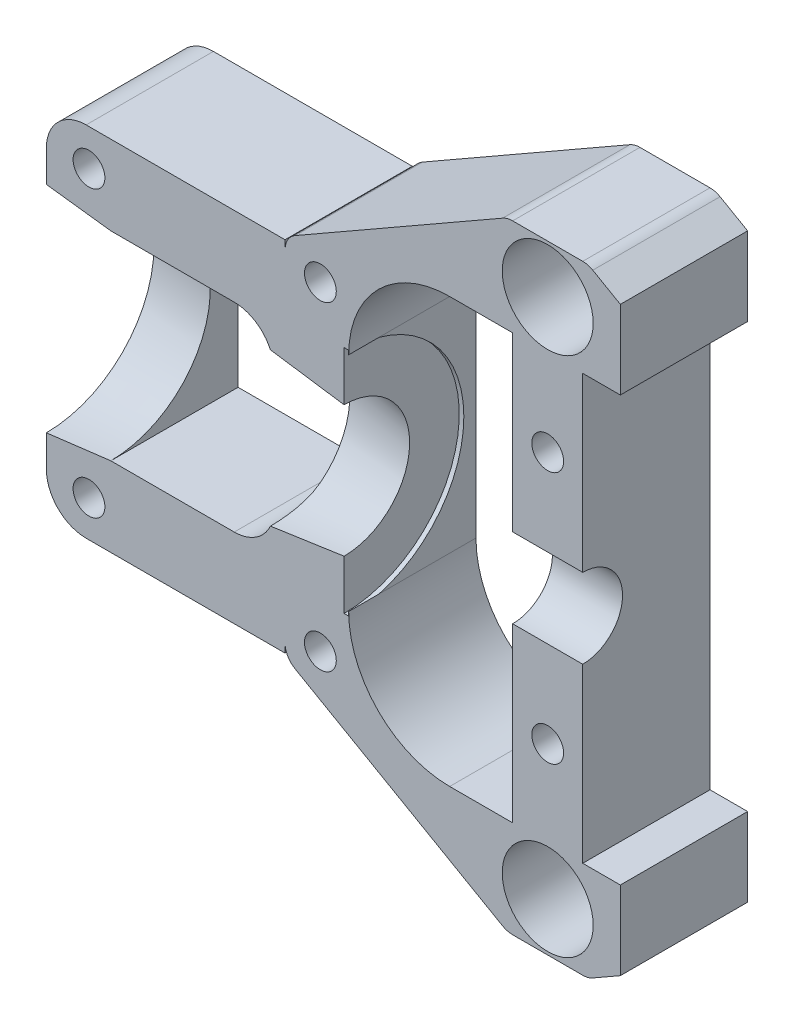
SolidWorks part; units mm, degrees
ref_plane "Front Plane" through (0, 0, 0) normal (0, 0, 1) x (1, 0, 0)
ref_plane "Top Plane" through (0, 0, 0) normal (0, 1, 0) x (1, 0, 0)
ref_plane "Right Plane" through (0, 0, 0) normal (1, 0, 0) x (0, 0, -1)
sketch "Sketch1" plane through (0, 0, 0) normal (0, 0, 1) x (1, 0, 0)
  line L0 (31.75, 34.925) -> (-31.75, 34.925) construction
  line L1 (-44.45, 22.225) -> (-44.45, -22.225) construction
  line L2 (-31.75, -34.925) -> (31.75, -34.925) construction
  line L3 (44.45, -22.225) -> (44.45, 22.225) construction
  line L4 (5.6665, -38.5261) -> (31.7424, -23.5917) construction
  line L5 (-33.02, -21.3876) -> (-33.02, 21.3876) construction
  line L6 (-31.7424, -23.5917) -> (-5.6665, -38.5261) construction
  line L7 (-4.4041, -38.862) -> (4.4041, -38.862) construction
  line L8 (33.02, -21.3876) -> (33.02, 21.3876) construction
  line L9 (5.6665, 38.5261) -> (31.7424, 23.5917) construction
  line L10 (-4.4041, 38.862) -> (4.4041, 38.862) construction
  line L11 (-5.6665, 38.5261) -> (-31.7424, 23.5917) construction
  line L12 (-33.02, -21.3876) -> (-33.02, 21.3876) construction
  line L13 (-33.02, -21.3876) -> (-33.02, 21.3876)
  line L14 (-5.6665, 38.5261) -> (-31.7424, 23.5917)
  line L15 (-4.4041, 38.862) -> (4.4041, 38.862)
  line L16 (5.6665, 38.5261) -> (31.7424, 23.5917)
  line L17 (33.02, -21.3876) -> (33.02, 21.3876)
  line L18 (-4.4041, -38.862) -> (4.4041, -38.862)
  line L19 (-31.7424, -23.5917) -> (-5.6665, -38.5261)
  line L20 (5.6665, -38.5261) -> (31.7424, -23.5917)
  line L21 (44.45, -22.225) -> (44.45, 22.225)
  line L22 (-31.75, -34.925) -> (31.75, -34.925)
  line L23 (-44.45, 22.225) -> (-44.45, -22.225)
  line L24 (31.75, 34.925) -> (-31.75, 34.925)
  line L25 (-12.319, 26.67) -> (12.319, 26.67) construction
  line L26 (25.019, 13.97) -> (25.019, -13.97) construction
  line L27 (-25.019, 13.97) -> (-25.019, -13.97) construction
  line L28 (-12.319, -26.67) -> (12.319, -26.67) construction
  line L29 (-12.319, 26.67) -> (12.319, 26.67)
  line L30 (25.019, 13.97) -> (25.019, -13.97)
  line L31 (-25.019, 13.97) -> (-25.019, -13.97)
  line L32 (-12.319, -26.67) -> (12.319, -26.67)
  line L33 (33.02, -15.875) -> (24.8753, -15.875)
  line L34 (33.02, 15.875) -> (24.8753, 15.875)
  line L35 (24.8753, 15.875) -> (24.8753, -15.875)
  line L36 (33.02, -15.875) -> (33.02, 15.875)
  line L37 (-33.02, -21.3876) -> (-33.02, 21.3876)
  line L38 (-33.02, -15.875) -> (-24.8753, -15.875)
  line L39 (-33.02, 15.875) -> (-24.8753, 15.875)
  line L40 (-33.02, 15.875) -> (-33.02, -15.875)
  line L41 (-24.8753, -15.875) -> (-24.8753, 15.875)
  line L42 (-4.4041, -38.862) -> (-4.4041, 38.862)
  line L43 (4.4041, -38.862) -> (4.4041, 38.862)
  line L44 (-12.319, 26.67) -> (12.319, 26.67) construction
  line L45 (-12.319, 26.67) -> (12.319, 26.67)
  line L46 (0, 27.051) -> (4.4041, 27.051)
  line L47 (0, 27.051) -> (-4.4041, 27.051)
  line L48 (0, -27.051) -> (-4.4041, -27.051)
  line L49 (0, -27.051) -> (4.4041, -27.051)
  line L50 (-1000, 0) -> (49000, 0) construction
  line L51 (0, -1000) -> (0, 49000) construction
  line L52 (9.1318, -26.67) -> (9.1318, -36.5414)
  line L53 (9.1318, 26.67) -> (9.1318, 36.5414)
  line L54 (-13.97, -1015.875) -> (-13.97, 48984.125) construction
  line L55 (-57.6639, -17.9107) -> (-57.6639, 17.9107) construction
  line L56 (-33.02, -22.5) -> (-63.02, -22.5)
  line L57 (-33.02, -22.5) -> (-33.02, 22.5)
  line L58 (-33.02, 22.5) -> (-63.02, 22.5)
  line L59 (-63.02, -22.5) -> (-63.02, 22.5)
  arc A0 (-5.6665, -38.5261) -> (-4.4041, -38.862) centre (-4.4041, -36.322) ccw construction
  arc A1 (-31.75, 34.925) -> (-44.45, 22.225) centre (-31.75, 22.225) ccw construction
  arc A2 (-44.45, -22.225) -> (-31.75, -34.925) centre (-31.75, -22.225) ccw construction
  arc A3 (31.75, -34.925) -> (44.45, -22.225) centre (31.75, -22.225) ccw construction
  arc A4 (44.45, 22.225) -> (31.75, 34.925) centre (31.75, 22.225) ccw construction
  arc A5 (31.7424, -23.5917) -> (33.02, -21.3876) centre (30.48, -21.3876) ccw construction
  arc A6 (33.02, 21.3876) -> (31.7424, 23.5917) centre (30.48, 21.3876) ccw construction
  arc A7 (5.6665, 38.5261) -> (4.4041, 38.862) centre (4.4041, 36.322) ccw construction
  arc A8 (-4.4041, 38.862) -> (-5.6665, 38.5261) centre (-4.4041, 36.322) ccw construction
  arc A9 (-31.7424, 23.5917) -> (-33.02, 21.3876) centre (-30.48, 21.3876) ccw construction
  arc A10 (-33.02, -21.3876) -> (-31.7424, -23.5917) centre (-30.48, -21.3876) ccw construction
  arc A11 (-33.02, -21.3876) -> (-31.7424, -23.5917) centre (-30.48, -21.3876) ccw
  arc A12 (-31.7424, 23.5917) -> (-33.02, 21.3876) centre (-30.48, 21.3876) ccw
  arc A13 (-4.4041, 38.862) -> (-5.6665, 38.5261) centre (-4.4041, 36.322) ccw
  arc A14 (5.6665, 38.5261) -> (4.4041, 38.862) centre (4.4041, 36.322) ccw
  arc A15 (33.02, 21.3876) -> (31.7424, 23.5917) centre (30.48, 21.3876) ccw
  arc A16 (31.7424, -23.5917) -> (33.02, -21.3876) centre (30.48, -21.3876) ccw
  arc A17 (-5.6665, -38.5261) -> (-4.4041, -38.862) centre (-4.4041, -36.322) ccw
  arc A18 (44.45, 22.225) -> (31.75, 34.925) centre (31.75, 22.225) ccw
  arc A19 (31.75, -34.925) -> (44.45, -22.225) centre (31.75, -22.225) ccw
  arc A20 (-44.45, -22.225) -> (-31.75, -34.925) centre (-31.75, -22.225) ccw
  arc A21 (-31.75, 34.925) -> (-44.45, 22.225) centre (-31.75, 22.225) ccw
  arc A22 (-12.319, 26.67) -> (-25.019, 13.97) centre (-12.319, 13.97) ccw construction
  arc A23 (25.019, 13.97) -> (12.319, 26.67) centre (12.319, 13.97) ccw construction
  arc A24 (12.319, -26.67) -> (25.019, -13.97) centre (12.319, -13.97) ccw construction
  arc A25 (-25.019, -13.97) -> (-12.319, -26.67) centre (-12.319, -13.97) ccw construction
  arc A26 (-12.319, 26.67) -> (-25.019, 13.97) centre (-12.319, 13.97) ccw
  arc A27 (25.019, 13.97) -> (12.319, 26.67) centre (12.319, 13.97) ccw
  arc A28 (12.319, -26.67) -> (25.019, -13.97) centre (12.319, -13.97) ccw
  arc A29 (-25.019, -13.97) -> (-12.319, -26.67) centre (-12.319, -13.97) ccw
  circle A30 centre (0, -32.766) radius 5.715 construction
  circle A31 centre (0, 32.766) radius 5.715 construction
  circle A32 centre (-13.97, -15.875) radius 9.2075 construction
  circle A33 centre (-13.97, 15.875) radius 9.2075 construction
  circle A34 centre (13.97, 15.875) radius 9.2075 construction
  circle A35 centre (13.97, -15.875) radius 9.2075 construction
  circle A36 centre (0, -32.766) radius 5.715
  circle A37 centre (0, 32.766) radius 5.715
  circle A38 centre (-13.97, -15.875) radius 9.2075
  circle A39 centre (-13.97, 15.875) radius 9.2075
  circle A40 centre (13.97, 15.875) radius 9.2075
  circle A41 centre (13.97, -15.875) radius 9.2075
  arc A42 (4.4041, -38.862) -> (5.6665, -38.5261) centre (4.4041, -36.322) ccw construction
  arc A43 (4.4041, -38.862) -> (5.6665, -38.5261) centre (4.4041, -36.322) ccw
  circle A44 centre (28.575, 20.0961) radius 2
  circle A45 centre (-28.575, -15.875) radius 3.175 construction
  circle A46 centre (-28.575, -15.875) radius 3.175
  circle A47 centre (-28.575, 15.875) radius 3.175 construction
  circle A48 centre (-28.575, 15.875) radius 3.175
  circle A49 centre (28.575, -15.875) radius 3.175 construction
  circle A50 centre (28.575, -15.875) radius 3.175
  circle A51 centre (28.575, 15.875) radius 3.175 construction
  circle A52 centre (28.575, 15.875) radius 3.175
  circle A53 centre (28.575, 20.0961) radius 3.025
  circle A54 centre (28.575, -20.0961) radius 3.025
  circle A55 centre (28.575, -20.0961) radius 2
  circle A56 centre (-28.575, -20.0961) radius 2
  circle A57 centre (-28.575, -20.0961) radius 3.025
  circle A58 centre (-28.575, 20.0961) radius 3.025
  circle A59 centre (-28.575, 20.0961) radius 2
  circle A60 centre (0, -15.875) radius 2
  circle A61 centre (0, -15.875) radius 3.025
  circle A62 centre (0, 15.875) radius 2
  circle A63 centre (0, 15.875) radius 3.025
  circle A64 centre (-57.6639, 17.9107) radius 3.025
  circle A65 centre (-57.6639, 17.9107) radius 2
  circle A66 centre (-57.6639, -17.9107) radius 3.025
  circle A67 centre (-57.6639, -17.9107) radius 2
  point P121 (0, 15.875)
  point P128 (-63.02, 0)
  point P137 (-57.6639, 0)
  dimension "D1" = 6.05
  dimension "D2" = 4
  dimension "D3" = 4
  dimension "D4" = 6.05
  dimension "D5" = 30
  dimension "D6" = 45
extrude "Boss-Extrude1" add sketch "Sketch1" along normal blind 16 contours L43 A43 L20 L22 A36 | A36 L42 L18 L43 | A46 L38 L13 A11 L19 L22 A36 L42 L32 A29 | A36 L22 L19 A17 L42 | A36 L43 L32 L42 | A37 L24 L16 A14 L43 | A37 L43 L15 L42 | A48 L39 A26 L29 L42 A37 L24 L14 A12 L13 | A37 L42 A13 L14 L24 | A37 L42 L29 L43 | A37 L42 L47 | A37 L46 L43 | A36 L43 L49 | A36 L48 L42 | L38 A46 | A48 A59 A58 | A46 A56 | A46 A56 | A46 A57 A56 | A46 A57 A56 | A36 L22 L52 L32 L43 | A37 L43 L29 L53 L24 | L38 A46 | A48 L39 L37 L38 A46 A29 L31 A26 | L32 L43 L29 L42 | A59 A48 | A48 A59 A58 | A59 A48 | A60 | A61 A60 | A62 | A63 A62 | L40 L58 L23 L56 | L59 L56 L23 L58 | A64 A65 | A66 A67 | A48 region at (-38.735, 0, 0) region at (-17.5272, -27.3539, 0) region at (-29.0794, 0, 0) region at (-17.5272, 27.3539, 0) region at (-28.575, -14.5275, 0) region at (-28.575, -16.6784, 0) region at (-53.4447, 0, 0) region at (-7.0498, -36.3818, 0) region at (-28.575, -17.8362, 0) region at (-30.4999, -18.4982, 0) region at (-29.6164, 22.8523, 0) region at (-28.575, 17.8362, 0) region at (-28.575, -18.5956, 0) region at (-28.575, -20.3596, 0) region at (-4.3127, -37.635, 0) region at (-3.347, -27.6473, 0) region at (-7.0498, 36.3818, 0) region at (-28.575, 20.3596, 0) region at (-28.575, 18.5956, 0) region at (6.525, -36.5411, 0) region at (0, -26.8605, 0) region at (3.347, -27.6473, 0) region at (0, 0, 0) region at (7.0829, -30.5135, 0) region at (0, 38.7706, 0) region at (-3.347, 27.6473, 0) region at (0, 26.8605, 0) region at (6.525, 36.5411, 0) region at (3.347, 27.6473, 0) region at (7.0829, 30.5135, 0) region at (0, -15.875, 0) region at (-2.9394, -15.875, 0) region at (0, 15.875, 0) region at (-2.9394, 15.875, 0) region at (-60.6033, 17.9107, 0) region at (-60.6033, -17.9107, 0)
sketch "Sketch9" plane through (-33.02, 0, 0) normal (1, 0, 0) x (0, 0, -1)
  line L2 (-1000, -21.9438) -> (49000, -21.9438) construction
  line L3 (0, -21.3876) -> (0, -22.5) construction
  circle A0 centre (16, 0) radius 12.15
  point P12 (0, -21.9438)
  dimension "D1" = 24.3
  dimension "D2" = 16
extrude "Cut-Extrude13" cut sketch "Sketch1<7>" along normal through all contours A60 | A62 | A59 A48 | A59 A48 | A46 A56 | A46 A56 region at (-28.575, -18.5956, 0) region at (-28.575, -20.3596, 0) region at (-28.575, 20.3596, 0) region at (-28.575, 18.5956, 0) region at (0, -15.875, 0) region at (0, 15.875, 0)
sketch "Sketch1<7>" plane through (0, 0, 0) normal (0, 0, 1) x (1, 0, 0) same geometry as "Sketch1"
extrude "Cut-Extrude14" cut sketch "Sketch1<8>" along normal blind 10.2 contours A46 A57 A56 | A46 A57 A56 | A48 A59 A58 | A48 A59 A58 | A63 A62 | A61 A60 | A64 A65 | A66 A67 region at (-28.575, -17.8362, 0) region at (-30.4999, -18.4982, 0) region at (-29.6164, 22.8523, 0) region at (-28.575, 17.8362, 0) region at (-2.9394, -15.875, 0) region at (-2.9394, 15.875, 0) region at (-60.6033, 17.9107, 0) region at (-60.6033, -17.9107, 0)
sketch "Sketch1<8>" plane through (0, 0, 0) normal (0, 0, 1) x (1, 0, 0) same geometry as "Sketch1"
sketch "Sketch12" plane through (0, 0, 16) normal (0, 0, 1) x (1, 0, 0)
  line L0 (-1000, 0) -> (49000, 0) construction
  line L1 (-34.4041, 0) -> (-34.4041, 9.5275)
  line L2 (-4.4041, -26.67) -> (-4.4041, 26.67) construction
  line L3 (-25.5959, 0) -> (-25.5959, 8.24)
  line L4 (-4.4041, -26.67) -> (-4.4041, 26.67)
  line L5 (-34.4041, 0) -> (-25.5959, 0)
  line L6 (-34.4041, 9.5275) -> (-25.5959, 8.24)
  line L7 (-63.02, 0) -> (-63.02, 13.5188)
  line L8 (-54.9215, 0) -> (-54.9215, 12.5145)
  line L9 (-54.9215, 0) -> (-63.02, 0)
  line L10 (-54.9215, 12.5145) -> (-63.02, 13.5188)
  line L11 (-63.02, -15) -> (-63.02, 15) construction
  line L12 (-25.5959, 0) -> (-34.4041, 0)
  line L13 (-63.02, -15) -> (-63.02, 15)
  line L14 (-25.019, 13.97) -> (-25.019, -13.97) construction
  line L15 (-54.9215, -12.5145) -> (-34.4041, -12.5145)
  line L16 (-54.9215, -12.5145) -> (-54.9215, 12.5145)
  line L17 (-54.9215, 12.5145) -> (-34.4041, 12.5145)
  line L18 (-34.4041, -12.5145) -> (-34.4041, 12.5145)
  line L19 (-25.019, -14.4774) -> (-25.5959, -14.4774)
  line L20 (-25.019, -14.4774) -> (-25.019, 14.4774)
  line L21 (-25.019, 14.4774) -> (-25.5959, 14.4774)
  line L22 (-25.5959, -14.4774) -> (-25.5959, 14.4774)
  line L23 (-25.019, 13.97) -> (-25.019, -13.97)
  point P17 (-34.4041, 0)
  point P24 (-25.5959, 0)
  dimension "D1" = 9.5275
  dimension "D2" = 8.24
  dimension "D3" = 12.5145
  dimension "D4" = 13.5188
  dimension "D5" = 8.0985
  dimension "D6" = 8.8083
  dimension "D7" = 30
  dimension "D8" = 25.029
revolve "Cut-Revolve1" cut sketch "Sketch12" angle 360 about L0 region at (-30.1064, 4.4496, 16) region at (-25.3074, 0, 16) region at (-59.0228, 6.5115, 16) reverse direction yes
sketch "Sketch13" plane through (0, 0, 16) normal (0, 0, 1) x (1, 0, 0)
  line L0 (-54.9215, -12.5145) -> (-54.9215, 12.5145) construction
  line L1 (-54.9215, -12.5145) -> (-54.9215, 12.5145)
  line L2 (-34.4041, -9.5275) -> (-34.4041, 9.5275) construction
  line L3 (-34.4041, -12.5155) -> (-54.9215, -12.5155)
  line L4 (-34.4041, -12.5155) -> (-34.4041, 12.5145)
  line L5 (-34.4041, 12.5145) -> (-54.9215, 12.5145)
  line L6 (-54.9215, -12.5155) -> (-54.9215, 12.5145)
  line L7 (-34.4041, -9.5275) -> (-34.4041, 9.5275)
  line M7 (-54.9215, 12.5145) -> (-54.9215, -12.5145)
  line M45 (-34.4041, -9.5275) -> (-34.4041, 9.5275)
  dimension "D1" = 25.03
extrude "Cut-Extrude15" cut sketch "Sketch13" against normal through all contours L6 L3 L4 L5 M45 M7 region at (-44.6628, -0.0005, 16)
fillet "Fillet2" radius 5 4 edges at (-63.02, -22.5, 8) (-63.02, 22.5, 8) (-34.4041, -12.5155, 8) (-34.4041, 12.5145, 8)
sketch "Sketch15" plane through (4.4041, 0, 0) normal (1, 0, 0) x (0, 0, -1)
  line L0 (-1000, 0) -> (49000, 0) construction
  line L1 (0, -26.67) -> (0, 26.67) construction
  line L2 (-16, -26.67) -> (-16, 26.67) construction
  line L3 (-16, -26.67) -> (-16, 26.67)
  circle A0 centre (-16, 0) radius 5
  point P5 (0, 0)
  line M5 (-16, 26.67) -> (-16, -26.67)
  dimension "D1" = 10
extrude "Cut-Extrude17" cut sketch "Sketch15" against normal blind 10 contours L0 A0 M5 | L3 L0 A0 | A0 L0 L3 | L0 A0 M5 region at (4.4041, 2.1221, 18.1221) region at (4.4041, -2.1221, 18.1221) region at (4.4041, 2.1221, 13.8779) region at (4.4041, -2.1221, 13.8779)
equation "\"shaftLength\" = 143"
equation "\"shaftMaxDiameter\" = 26.25"
equation "\"shaftMinDiameter\" = 16"
equation "\"postKnobCatheterConnection\" = 12.5"
equation "\"servoHexagonDiameter\" = 15"
equation "\"servoHexagonArmThickness\" = 2.2"
equation "\"servoHexagonHeight\" = 20"
equation "\"servoHexagonSeparation\" = 33"
equation "\"servoCylinderDiameter\" = 8"
equation "\"aurisSheathHeight\" = 16"
equation "\"platformWidth\" = 60"
equation "\"platformLength\" = 60"
equation "\"frontCylinderLength\" = 10"
equation "\"D1@Sketch9\"=24.3"
equation "\"knobMinDiameter\" = 13"
equation "\"knobMaxDiameter\" = 27"
equation "\"screwHeadDiameter\" = 6.05"
equation "\"screwShaftDiameter\" = 4"
equation "\"screwLength\" = 15"
equation "\"D1@Sketch1\"=\"screwHeadDiameter\""
equation "\"D2@Sketch1\"=\"screwShaftDiameter\""
equation "\"screwHeadThickness\" = 3"
equation "\"D1@Boss-Extrude1\"=\"aurisSheathHeight\""
equation "\"D2@Sketch9\"=\"aurisSheathHeight\""
equation "\"D1@Sketch12\"=1.03*(\"shaftMinDiameter\"+2.5)/2"
equation "\"D2@Sketch12\"=1.03*(\"shaftMinDiameter\")/2"
equation "\"D1@Cut-Extrude14\"=1.2*(\"aurisSheathHeight\"-\"screwLength\"/2)"
equation "\"D3@Sketch12\"=1.03*24.3/2"
equation "\"D4@Sketch12\"=1.03*\"shaftMaxDiameter\"/2"
equation "\"D3@Sketch1\"=\"screwShaftDiameter\""
equation "\"D4@Sketch1\"=\"screwHeadDiameter\""
equation "\"D8@Sketch12\"=1.03*24.3"
